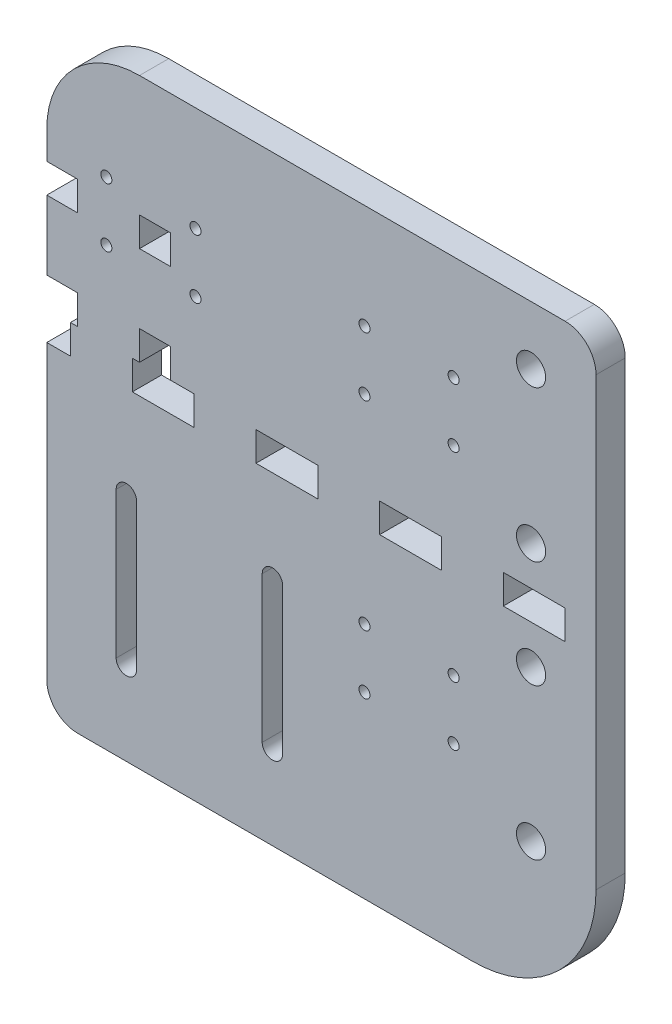
SolidWorks part; units mm, degrees
ref_plane "Front Plane" through (0, 0, 0) normal (0, 0, 1) x (1, 0, 0)
ref_plane "Top Plane" through (0, 0, 0) normal (0, 1, 0) x (1, 0, 0)
ref_plane "Right Plane" through (0, 0, 0) normal (1, 0, 0) x (0, 0, -1)
sketch "Sketch1" plane through (0, 0, 0) normal (0, 0, 1) x (-1, 0, 0)
  line L0 (5.4449, 19.1182) -> (-12.8627, 19.1182) construction
  line L1 (-15.4204, 35.8131) -> (8.0026, 35.8131) construction
  line L2 (-15.4204, 35.8131) -> (-15.4204, 14.5439) construction
  line L3 (-15.4204, 14.5439) -> (8.0026, 14.5439) construction
  line L4 (8.0026, 35.8131) -> (8.0026, 14.5439) construction
  line L5 (5.4449, 19.1182) -> (5.4449, 31.2335) construction
  line L6 (5.4449, 31.2335) -> (-12.8627, 31.2335) construction
  line L7 (-12.8627, 31.2335) -> (-12.8627, 19.1182) construction
  line L8 (-15.4204, 14.5439) -> (-15.4204, -17.2061) construction
  line L9 (-35.7704, 4.6785) -> (-35.7704, 45.6785) construction
  line L10 (-35.7704, 45.6785) -> (-21.7704, 45.6785) construction
  line L11 (-21.7704, 45.6785) -> (-21.7704, 4.6785) construction
  line L12 (-21.7704, 4.6785) -> (-35.7704, 4.6785) construction
  line L13 (-1015.4204, -1.3311) -> (48984.5796, -1.3311) construction
  line L14 (-15.4204, 25.1785) -> (-21.7704, 25.1785)
  line L15 (-21.7704, -7.3406) -> (-35.7704, -7.3406) construction
  line L16 (-21.7704, -48.3406) -> (-21.7704, -7.3406) construction
  line L17 (-35.7704, -48.3406) -> (-21.7704, -48.3406) construction
  line L18 (-35.7704, -7.3406) -> (-35.7704, -48.3406) construction
  line L19 (-12.8627, -33.8956) -> (-12.8627, -21.7803) construction
  line L20 (5.4449, -33.8956) -> (-12.8627, -33.8956) construction
  line L21 (5.4449, -21.7803) -> (5.4449, -33.8956) construction
  line L22 (8.0026, -38.4752) -> (8.0026, -17.2061) construction
  line L23 (-15.4204, -17.2061) -> (8.0026, -17.2061) construction
  line L24 (-15.4204, -38.4752) -> (-15.4204, -17.2061) construction
  line L25 (-15.4204, -38.4752) -> (8.0026, -38.4752) construction
  line L26 (5.4449, -21.7803) -> (-12.8627, -21.7803) construction
  line L27 (-15.4204, -27.8406) -> (-21.7704, -27.8406)
  line L28 (-15.4204, -1.3311) -> (-15.4204, 8.6689) construction
  line L29 (39.3526, 8.6689) -> (39.3526, 61.6689) construction
  line L30 (70.7026, -4.3283) -> (70.7026, -10.9042)
  line L31 (14.3526, 8.6689) -> (14.3526, 61.6689) construction
  line L32 (14.3526, 61.6689) -> (64.3526, 61.6689) construction
  line L33 (64.3526, 61.6689) -> (64.3526, 8.6689) construction
  line L34 (64.3526, 8.6689) -> (14.3526, 8.6689) construction
  line L35 (24.3526, 50.6689) -> (24.3526, 20.6689) construction
  line L36 (24.3526, 61.6689) -> (24.3526, 50.6689) construction
  line L37 (24.3526, 20.6689) -> (24.3526, 50.6689) construction
  line L38 (22.2526, 20.6689) -> (22.2526, 50.6689)
  line L39 (26.4526, 20.6689) -> (26.4526, 50.6689)
  line L40 (54.3526, 50.6689) -> (54.3526, 20.6689) construction
  line L41 (54.3526, 20.6689) -> (54.3526, 50.6689) construction
  line L42 (56.4526, 20.6689) -> (56.4526, 50.6689)
  line L43 (52.2526, 20.6689) -> (52.2526, 50.6689)
  line L44 (-35.7704, -4.3283) -> (-35.7704, 1.6661)
  line L45 (-35.7704, 1.6661) -> (-23.0704, 1.6661)
  line L46 (-23.0704, 1.6661) -> (-23.0704, -4.3283)
  line L47 (40.1564, -33.8956) -> (40.1564, -21.7803) construction
  line L48 (-10.3704, -4.3283) -> (-10.3704, 1.6661)
  line L49 (64.3526, 68.0189) -> (-16.7204, 68.0189)
  line L50 (70.7026, 61.6689) -> (70.7026, 1.6661)
  line L51 (26.2526, -55.3542) -> (-35.7704, -55.3542)
  line L52 (-42.1204, 42.6189) -> (-42.1204, -49.0042)
  line L53 (-10.3704, 1.6661) -> (2.3296, 1.6661)
  line L54 (2.3296, 1.6661) -> (2.3296, -4.3283)
  line L55 (58.4641, -33.8956) -> (40.1564, -33.8956) construction
  line L56 (15.0296, -4.3283) -> (15.0296, 1.6661)
  line L57 (15.0296, 1.6661) -> (27.7296, 1.6661)
  line L58 (27.7296, 1.6661) -> (27.7296, -4.3283)
  line L59 (58.4641, -21.7803) -> (58.4641, -33.8956) construction
  line L60 (40.4296, -4.3283) -> (40.4296, 1.6661)
  line L61 (40.4296, 1.6661) -> (53.1296, 1.6661)
  line L62 (53.1296, 1.6661) -> (53.1296, -4.3283)
  line L63 (61.0218, -38.4752) -> (61.0218, -17.2061) construction
  line L64 (65.8296, -4.3283) -> (65.8296, 1.6661)
  line L65 (65.8296, 1.6661) -> (70.7026, 1.6661)
  line L66 (65.8296, -4.3283) -> (70.7026, -4.3283)
  line L67 (40.4296, -4.3283) -> (53.1296, -4.3283)
  line L68 (15.0296, -4.3283) -> (27.7296, -4.3283)
  line L69 (-10.3704, -4.3283) -> (2.3296, -4.3283)
  line L70 (-35.7704, -4.3283) -> (-23.0704, -4.3283)
  line L71 (37.5987, -17.2061) -> (61.0218, -17.2061) construction
  line L72 (37.5987, -38.4752) -> (37.5987, -17.2061) construction
  line L73 (37.5987, -38.4752) -> (61.0218, -38.4752) construction
  line L74 (58.4641, -21.7803) -> (40.1564, -21.7803) construction
  line L75 (26.2526, -55.3542) -> (45.3026, -55.3542)
  line L76 (70.7026, -30.5523) -> (70.7026, -36.3042)
  line L77 (70.7026, -29.9542) -> (70.7026, -10.9042)
  line L78 (64.3526, -4.3283) -> (70.7026, -4.3283)
  line L79 (64.3526, -4.3283) -> (64.3526, -10.3283)
  line L80 (64.3526, -10.3283) -> (70.7026, -10.3283)
  line L81 (70.7026, -4.3283) -> (70.7026, -10.3283)
  line L82 (45.3026, -4.3283) -> (51.6526, -4.3283)
  line L83 (45.3026, -4.3283) -> (45.3026, -10.3283)
  line L84 (45.3026, -10.3283) -> (51.6526, -10.3283)
  line L85 (51.6526, -4.3283) -> (51.6526, -10.3283)
  line L86 (45.3026, -24.5523) -> (51.6526, -24.5523)
  line L87 (45.3026, -24.5523) -> (45.3026, -30.5523)
  line L88 (45.3026, -30.5523) -> (51.6526, -30.5523)
  line L89 (51.6526, -24.5523) -> (51.6526, -30.5523)
  line L90 (64.3526, -24.5523) -> (70.7026, -24.5523)
  line L91 (64.3526, -24.5523) -> (64.3526, -30.5523)
  line L92 (64.3526, -30.5523) -> (70.7026, -30.5523)
  line L93 (70.7026, -24.5523) -> (70.7026, -30.5523)
  line L94 (51.6526, -55.3542) -> (45.3026, -55.3542)
  line L95 (45.3026, -55.3542) -> (45.4172, -55.5387)
  circle A0 centre (-12.8627, 31.2335) radius 1.1321
  circle A1 centre (5.4449, 31.2335) radius 1.1321
  circle A2 centre (5.4449, 19.1182) radius 1.1321
  circle A3 centre (-12.8627, 19.1182) radius 1.1321
  circle A4 centre (-28.7704, -43.3406) radius 3
  circle A5 centre (-28.7704, -12.3406) radius 3
  circle A6 centre (-12.8627, -21.7803) radius 1.1321
  circle A7 centre (5.4449, -21.7803) radius 1.1321
  circle A8 centre (-28.7704, 9.6785) radius 3
  circle A9 centre (-28.7704, 40.6785) radius 3
  circle A10 centre (5.4449, -33.8956) radius 1.1321
  circle A11 centre (-12.8627, -33.8956) radius 1.1321
  arc A12 (22.2526, 20.6689) -> (26.4526, 20.6689) centre (24.3526, 20.6689) ccw
  arc A13 (26.4526, 50.6689) -> (22.2526, 50.6689) centre (24.3526, 50.6689) ccw
  arc A14 (56.4526, 20.6689) -> (52.2526, 20.6689) centre (54.3526, 20.6689) cw
  arc A15 (52.2526, 50.6689) -> (56.4526, 50.6689) centre (54.3526, 50.6689) cw
  arc A16 (70.7026, -36.3042) -> (51.6526, -55.3542) centre (51.6526, -36.3042) cw
  arc A17 (-16.7204, 68.0189) -> (-42.1204, 42.6189) centre (-16.7204, 42.6189) ccw
  arc A18 (64.3526, 68.0189) -> (70.7026, 61.6689) centre (64.3526, 61.6689) cw
  arc A19 (-35.7704, -55.3542) -> (-42.1204, -49.0042) centre (-35.7704, -49.0042) cw
  circle A20 centre (40.1564, -21.7803) radius 1.1321
  circle A21 centre (58.4641, -21.7803) radius 1.1321
  circle A22 centre (58.4641, -33.8956) radius 1.1321
  circle A23 centre (40.1564, -33.8956) radius 1.1321
  point P42 (-15.4204, -1.3311)
  point P57 (24.3526, 35.6689)
  point P66 (54.3526, 35.6689)
  dimension "D8" = 19.05
  dimension "D9" = 25.4
  dimension "D10" = 6.35
  dimension "D11" = 6.35
  dimension "D1" = 21.2692
  dimension "D2" = 23.423
  dimension "D3" = 4.5742
  dimension "D4" = 2.5577
  dimension "D5" = 31.75
  dimension "D6" = 30
  dimension "D7" = 11
  dimension "D12" = 4
extrude "Boss-Extrude1" add sketch "Sketch1" along normal blind 5.9944 contours A19 L51 L50 A18 L49 A17 L52 A13 L39 A12 L38 A10 A9 A8 A6 A4 A3 A2 A1 A0 A5 A7 A11 L43 A15 L42 A14 region at (-13.8451, -6.0468, 0)
